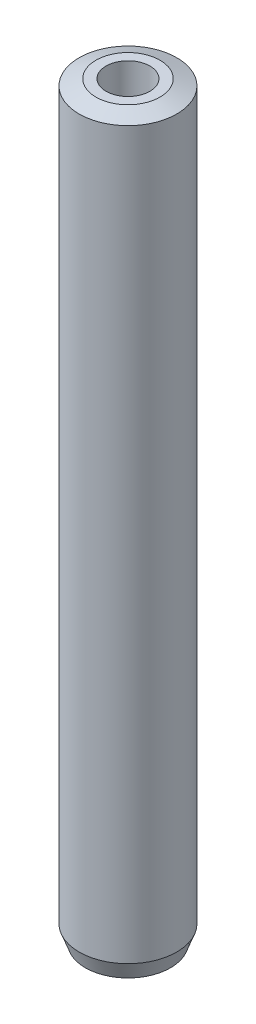
SolidWorks part; units mm, degrees
ref_plane "Front Plane" through (0, 0, 0) normal (0, 0, 1) x (1, 0, 0)
ref_plane "Top Plane" through (0, 0, 0) normal (0, 1, 0) x (1, 0, 0)
ref_plane "Right Plane" through (0, 0, 0) normal (1, 0, 0) x (0, 0, -1)
sketch "Sketch1" plane through (0, 0, 0) normal (0, 1, 0) x (1, 0, 0)
  circle A0 centre (0, 0) radius 22.5
  dimension "SHAFT_OD" = 45
extrude "Boss-Extrude1" add sketch "Sketch1" along normal blind 345.1925
sketch "Sketch2" plane through (0, 0, 0) normal (0, 1, 0) x (1, 0, 0)
  circle A0 centre (0, 0) radius 10.1086
  dimension "BORE_D" = 20.2172
extrude "Cut-Extrude1" cut sketch "Sketch2" along normal through all
chamfer "Chamfer1" distance 2.875 angle 69.638 2 edges at (0, 345.1925, 22.5) (0, 0, 22.5) first distance on face at (0, 345.1925, 22.5) first distance on face at (0, 0, 10.1086)
